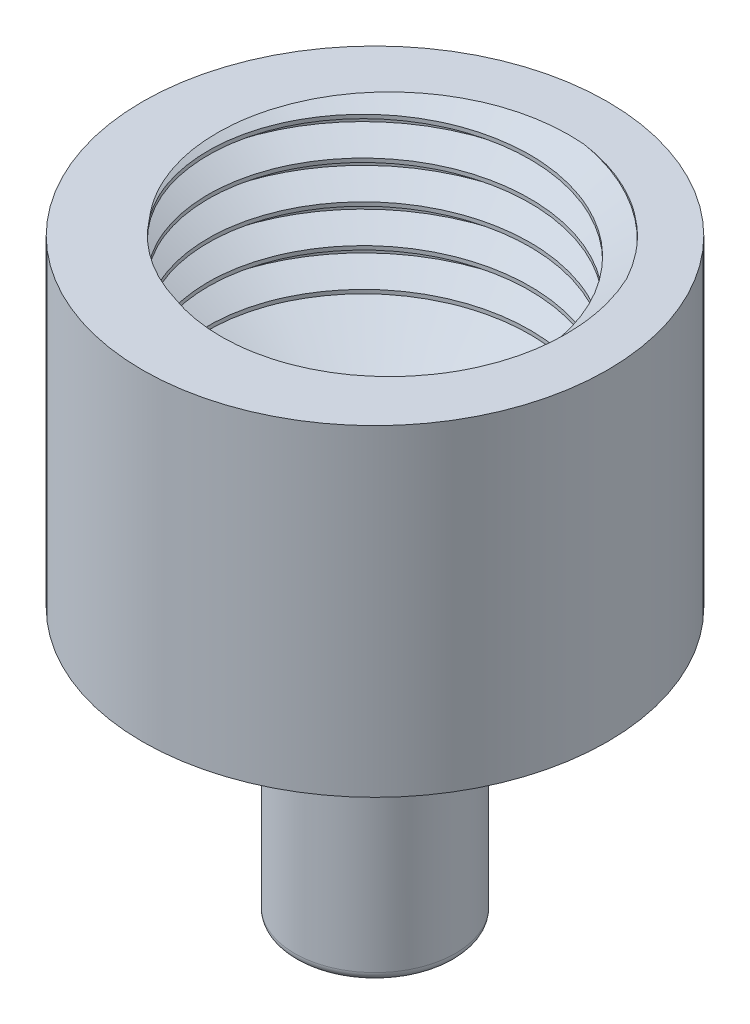
SolidWorks part; units mm, degrees
ref_plane "Front Plane" through (0, 0, 0) normal (0, 0, 1) x (1, 0, 0)
ref_plane "Top Plane" through (0, 0, 0) normal (0, 1, 0) x (1, 0, 0)
ref_plane "Right Plane" through (0, 0, 0) normal (1, 0, 0) x (0, 0, -1)
sketch "Sketch1" plane through (0, 0, 0) normal (0, 1, 0) x (1, 0, 0)
  circle A0 centre (0, 0) radius 6.5
  circle A1 centre (0, 0) radius 1
  dimension "D1" = 13
  dimension "D2" = 2
extrude "Boss-Extrude1" add sketch "Sketch1" along normal blind 2
sketch "Sketch2" plane through (0, 2, 0) normal (0, 1, 0) x (1, 0, 0)
  circle A0 centre (0, 0) radius 6.5 construction
  circle A1 centre (0, 0) radius 6.5
  circle A2 centre (0, 0) radius 4.5
  dimension "D1" = 9
extrude "Boss-Extrude2" add sketch "Sketch2" along normal blind 7
thread "Thread1" pitch 1.27 method cut profile "Thread Profile1" start angle 0, offset 0, length 0, pitch 1.06, diameter 9
ref_plane "Plane1" through (4.5, 2, 0) normal (0, 0, 1) x (1, 0, 0)
sketch "Thread Profile1" plane through (4.5, 2, 0) normal (0, 0, 1) x (1, 0, 0)
  line L0 (0, 0) -> (0, 1.27) construction
  line L1 (0, 0) -> (0.6874, 0.3969)
  line L2 (0.6874, 0.3969) -> (0.6874, 0.5556)
  line L3 (0.6874, 0.5556) -> (0, 0.9525)
  line L4 (0.6874, 0.4762) -> (0, 0.4762) construction
  line L11 (0, 0) -> (0, 0.9525)
  point P2 (0, 0)
  dimension "Pitch" = 1.27
  dimension "Profile_Angle" = 60
  dimension "Profile_Land" = 0.1588
  dimension "Profile_Height" = 0.6874
sketch "Sketch5" plane through (0, 0, 0) normal (0, -1, 0) x (1, 0, 0)
  circle A0 centre (0, 0) radius 1 construction
  circle A1 centre (0, 0) radius 1
  circle A2 centre (0, 0) radius 2.25
  dimension "D1" = 4.5
extrude "Boss-Extrude3" add sketch "Sketch5" along normal blind 7.5
fillet "Fillet1" radius 2 1 edges at (0, 0, 2.25)
fillet "Fillet2" radius 0.25 1 edges at (0, -7.5, -2.25)
sketch "Sketch6" plane through (0, 0, 0) normal (1, 0, 0) x (0, 0, -1)
  line L0 (-1, 2) -> (-6.5, 5.1754)
  line L1 (-6.5, 9) -> (-6.5, 0) construction
  line L2 (-6.5, 5.1754) -> (-6.5, 0)
  line L3 (-6.5, 0) -> (-1, 0)
  line L4 (1, 2) -> (-1, 2) construction
  line L5 (1, 2) -> (-1, 2) construction
  line L6 (-1, 2) -> (-1, 0) construction
  line L7 (-1, 0) -> (-1, 2)
  dimension "D1" = 30
ref_axis "Axis1" through (0, 13, 0) along (0, -1, 0)
revolve "Revolve1" add sketch "Sketch6" angle 360 about axis through (0, 13, 0) along (0, -1, 0)
